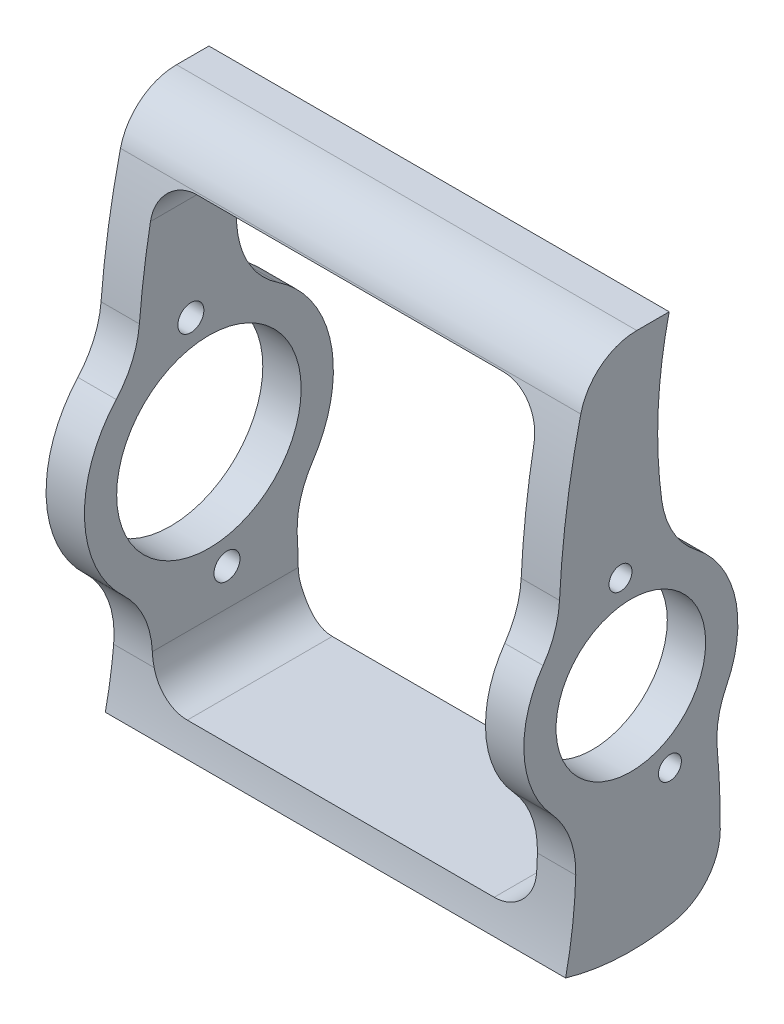
SolidWorks part; units mm, degrees
other "Markup2"
sketch "Sketch9" plane through (31.75, 50.4016, 20.35) normal (0.8402, 0.4575, 0.2911) x (0.3274, 0, -0.9449)
material "AISI 4340 Steel, normalized"
ref_plane "Front Plane" through (0, 0, 0) normal (0, 0, 1) x (1, 0, 0)
ref_plane "Top Plane" through (0, 0, 0) normal (0, 1, 0) x (1, 0, 0)
ref_plane "Right Plane" through (0, 0, 0) normal (1, 0, 0) x (0, 0, -1)
other "Center of Mass"
sketch "Weapon Layout" plane through (0, 0, 0) normal (1, 0, 0) x (0, 0, -1)
  line L0 (-6.35, 50.4016) -> (6.35, 50.4016) construction
  line L1 (-10.8026, -36.5365) -> (14.5626, -35.2071) construction
  line L2 (6.35, 50.4016) -> (-5.4537, 0) construction
  line L3 (6.35, 50.4016) -> (0, 0) construction
  line L4 (0, 0) -> (0, -35.9703) construction
  circle A0 centre (0, 0) radius 14 construction
  circle A1 centre (0, 0) radius 50.8 construction
  circle A2 centre (0, 0) radius 17.175 construction
  circle A3 centre (0, 0) radius 20.35 construction
  arc A4 (-6.35, 50.4016) -> (-20.35, 0) centre (77.3756, 0) ccw construction
  arc A5 (25.0504, -28.707) -> (-25.4024, -28.3959) centre (0, 0) cw construction
  arc A6 (6.35, 50.4016) -> (15.4347, 13.2625) centre (47.4536, 40.7754) ccw construction
  dimension "D1" = 28
  dimension "D2" = 101.6
  dimension "D3" = 3.175
  dimension "D4" = 6.35
  dimension "D5" = 12.7
  dimension "D7" = 6
  dimension "D6" = 12.7
  dimension "D8" = 25.4
  dimension "D9" = 87
sketch "Sketch2" plane through (0, 0, 0) normal (1, 0, 0) x (0, 0, -1)
  line L0 (-6.35, 50.4016) -> (6.35, 50.4016)
  line L1 (-11.3119, -1.6391) -> (0, 0) construction
  line L2 (6.35, 50.4016) -> (-5.4537, 0) construction
  line L3 (-11.6027, 1.0256) -> (-15.24, 50.4016) construction
  arc A0 (-10.8026, -36.5365) -> (14.5626, -35.2071) centre (0, 0) ccw
  arc A1 (-25.4024, -28.3959) -> (25.0504, -28.707) centre (0, 0) ccw construction
  arc A2 (-10.8344, -4.2769) -> (-11.6027, 1.0256) centre (26.3943, 3.8247) cw
  arc A3 (9.8248, 6.4214) -> (11.7322, 0.3423) centre (-25.4469, -7.9841) cw
  arc A4 (-11.6027, 1.0256) -> (-6.35, 50.4016) centre (127.0686, 11.2409) cw
  arc A5 (-10.8344, -4.2769) -> (-10.8026, -36.5365) centre (-85.2917, -20.4799) cw
  arc A6 (6.35, 50.4016) -> (9.8248, 6.4214) centre (76.9988, 33.8561) ccw
  arc A7 (11.7322, 0.3423) -> (14.5626, -35.2071) centre (-112.198, -27.4122) cw
  circle A9 centre (0, 0) radius 11.43 construction
  point P25 (10.9058, 3.4217)
  dimension "D1" = 127
  dimension "D2" = 38.1
  dimension "D3" = 76.2
  dimension "D4" = 38.1
  dimension "D5" = 22.86
  dimension "D6" = 8.89
extrude "Boss-Extrude2" add sketch "Sketch2" along normal mid plane 76.2
sketch "Sketch3" plane through (0, 0, 0) normal (0, 0, 1) x (1, 0, 0)
  line L0 (38.1, 50.4016) -> (-38.1, 50.4016) construction
  line L1 (-31.75, 42.7816) -> (31.75, 42.7816)
  line L2 (-31.75, 42.7816) -> (-31.75, -31.75)
  line L3 (-31.75, -31.75) -> (31.75, -31.75)
  line L4 (31.75, 42.7816) -> (31.75, -31.75)
  line L6 (-38.1, -38.1) -> (38.1, -38.1) construction
  line L7 (-38.1, 50.4016) -> (-38.1, 1.0256) construction
  dimension "D4" = 6.35
  dimension "D1" = 7.62
  dimension "D3" = 6.35
  dimension "D2" = 6.35
extrude "Cut-Extrude1" cut sketch "Sketch3" against normal through all both and the other way through all
fillet "Fillet1" radius 6.35 4 edges at (-31.75, 42.7816, 1.6822) (31.75, 42.7816, 1.6822) (31.75, -31.75, -2.3991) (-31.75, -31.75, -2.3991)
fillet "Fillet3" radius 9.525 2 edges at (0, -35.2071, -14.5626) (0, 50.4016, 6.35)
sketch "Sketch6" plane through (-38.1, 0, 0) normal (-1, 0, 0) x (0, 0, 1)
  circle A0 centre (0, 0) radius 20.604
  dimension "D1" = 41.208
extrude "Boss-Extrude3" add sketch "Sketch6" against normal up to surface (6.35 mm away) up to face at (-31.75, 3.1892, 0.2294)
sketch "Sketch7" plane through (-38.1, 0, 0) normal (-1, 0, 0) x (0, 0, 1)
  circle A0 centre (0, 0) radius 15.27
  arc A1 (9.1181, -18.4766) -> (11.8655, 16.8444) centre (0, 0) ccw construction
  dimension "D1" = 30.54
extrude "Cut-Extrude3" cut sketch "Sketch7" against normal up to next
sketch "Sketch10" plane through (38.1, 0, 0) normal (1, 0, 0) x (0, 0, -1)
  circle A0 centre (0, 0) radius 17.7165
  dimension "D1" = 35.433
extrude "Boss-Extrude4" add sketch "Sketch10" against normal up to surface (6.35 mm away) up to face at (31.75, 3.1892, 0.2294)
sketch "Sketch5" plane through (38.1, 0, 0) normal (1, 0, 0) x (0, 0, -1)
  circle A0 centre (0, 0) radius 12.3825
  circle A1 centre (0, 0) radius 6.35 construction
  dimension "D1" = 12.7
  dimension "D2" = 24.765
extrude "Cut-Extrude2" cut sketch "Sketch5" against normal up to next
fillet "Fillet2" radius 15.24 8 edges at (-34.925, 16.8444, 11.8655) (-34.925, -18.4766, 9.1181) (-34.925, -14.9406, -14.1881) (-34.925, 19.765, -5.8198) (34.925, 16.4593, -6.5548) (34.925, -11.162, -13.7581) (34.925, -15.09, 9.2826) (34.925, 13.0644, 11.9665)
sketch "Sketch11" plane through (38.1, 0, 0) normal (1, 0, 0) x (0, 0, -1)
  circle A0 centre (-1.7114, 16.2614) radius 1.8986
  circle A1 centre (-1.7114, 16.2614) radius 1.8986 construction
  circle A2 centre (6.465, -15.0189) radius 1.8987
  circle A3 centre (6.465, -15.0189) radius 1.8986 construction
extrude "Cut-Extrude4" cut sketch "Sketch11" against normal up to surface (6.35 mm away) up to face at (31.75, 12.3825, 0)
hole_wizard "#6 Clearance Hole1" positions "Sketch12" profile "Sketch13" hole size "#6" standard "ANSI Inch"
sketch "Sketch12" plane through (-38.1, 0, 0) normal (1, 0, 0) x (0, 0, -1)
  point P0 (-2.9885, 19.3009)
  point P3 (2.9885, -19.3009)
sketch "Sketch13" plane through (-38.1, 19.3009, 2.9885) normal (0, 1, 0) x (0, 0, 1)
  line L0 (0, 0) -> (0, 8.9134)
  line L1 (0, 8.9134) -> (2.1526, 7.62)
  line L2 (2.1526, 7.62) -> (2.1526, 0)
  line L5 (2.1526, 0) -> (0, 0)
  line L10 (0, 8.9134) -> (-2.1527, 7.62) construction
  line L11 (0, -6.35) -> (0, 107.95) construction
  dimension "Hole Dia." = 4.3053
  dimension "Hole Depth" = 7.62
  dimension "Drill Angle" = 118
other "Center of Mass Reference Point1"
equation "\"D1@Weapon Layout\" = 28mm"
equation "\"D1@Sketch6\"=\"bearing OD L\"+.42in+0.1in"
equation "\"D2@Sketch3\"=\"D3@Sketch3\""
equation "\"D1@Sketch7\"=\"bearing OD L\"+0.1in"
equation "\"D2@Sketch5\"=\"bearing OD R\" + .1"
equation "\"D1@Sketch10\"=\"bearing OD R\" + 0.42 + .1"
equation "\"bearing OD R\"= 7 / 8"
equation "\"bearing OD L\"= 28mm"
